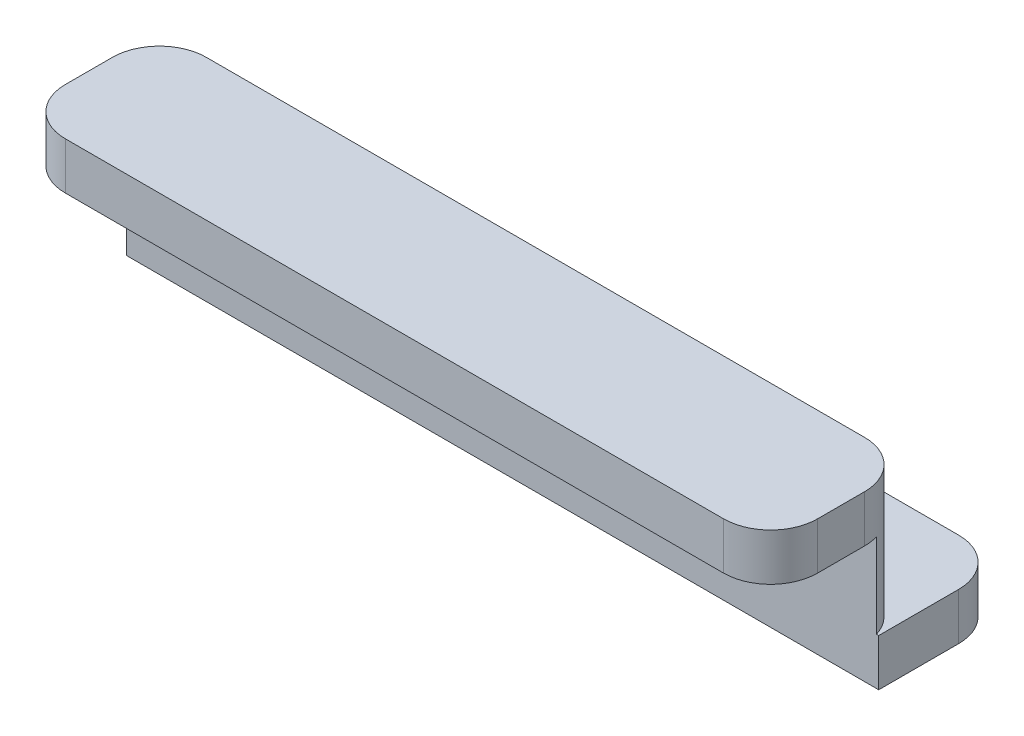
SolidWorks part; units mm, degrees
ref_plane "Front Plane" through (0, 0, 0) normal (0, 0, 1) x (1, 0, 0)
ref_plane "Top Plane" through (0, 0, 0) normal (0, 1, 0) x (1, 0, 0)
ref_plane "Right Plane" through (0, 0, 0) normal (1, 0, 0) x (0, 0, -1)
sketch "Sketch1" plane through (0, 0, 0) normal (0, 1, 0) x (1, 0, 0)
  line L1 (2, 0) -> (30, 0)
  line L2 (0, 2) -> (0, 4)
  line L3 (2, 6) -> (30, 6)
  line L4 (32, 2) -> (32, 4)
  arc A0 (30, 6) -> (32, 4) centre (30, 4) cw
  arc A1 (30, 0) -> (32, 2) centre (30, 2) ccw
  arc A2 (2, 0) -> (0, 2) centre (2, 2) cw
  arc A3 (0, 4) -> (2, 6) centre (2, 4) cw
  point P11 (0, 0)
  dimension "D1" = 2
  dimension "D2" = 2
  dimension "D3" = 32
  dimension "D4" = 6
extrude "Boss-Extrude1" add sketch "Sketch1" along normal blind 2
sketch "Sketch2" plane through (0, 2, 0) normal (0, 1, 0) x (1, 0, 0)
  line L0 (16, 0) -> (16, 10.7795) construction
  line L1 (2, 0) -> (30, 0) construction
  line L2 (32, 4) -> (32, 2)
  line L4 (0, 4) -> (0, 2) construction
  line L5 (30, 6) -> (2, 6) construction
  line L13 (0, 4) -> (0, 2)
  line L14 (30, 6) -> (2, 6)
  line L21 (30.1, 3.1) -> (30.1, 0.0025)
  line L22 (3.4, 4.6) -> (28.6, 4.6)
  line L23 (1.9, 0.0025) -> (1.9, 3.1)
  arc A0 (32, 2) -> (30.1, 0.0025) centre (30, 2) cw
  arc A1 (30, 6) -> (32, 4) centre (30, 4) cw
  arc A3 (2, 6) -> (0, 4) centre (2, 4) ccw construction
  arc A4 (0, 2) -> (2, 0) centre (2, 2) ccw construction
  arc A11 (2, 6) -> (0, 4) centre (2, 4) ccw
  arc A12 (0, 2) -> (1.9, 0.0025) centre (2, 2) ccw
  arc A15 (30.1, 3.1) -> (28.6, 4.6) centre (28.6, 3.1) ccw
  arc A16 (3.4, 4.6) -> (1.9, 3.1) centre (3.4, 3.1) ccw
  point P14 (16, 4.9)
  point P18 (32, 3)
  point P32 (16, 6)
  dimension "D2" = 1.9
  dimension "D3" = 1.5
  dimension "D1" = 1.4
extrude "Boss-Extrude2" add sketch "Sketch2" against normal blind 7.6
sketch "Sketch4" plane through (0, -5.6, 0) normal (0, -1, 0) x (1, 0, 0)
  line L5 (30, -6) -> (2, -6) construction
  line L8 (30, -6) -> (2, -6)
  line L9 (0, -4) -> (0, -8)
  line L10 (2, -10) -> (30, -10)
  line L11 (32, -8) -> (32, -4)
  arc A9 (30, -6) -> (32, -4) centre (30, -4) ccw construction
  arc A10 (0, -4) -> (2, -6) centre (2, -4) ccw construction
  arc A11 (30, -6) -> (32, -4) centre (30, -4) ccw
  arc A12 (0, -4) -> (2, -6) centre (2, -4) ccw
  arc A13 (0, -8) -> (2, -10) centre (2, -8) ccw
  arc A14 (30, -10) -> (32, -8) centre (30, -8) ccw
  dimension "D1" = 2
  dimension "D2" = 4
extrude "Boss-Extrude3" add sketch "Sketch4" against normal blind 2
sketch "Sketch5" plane through (0, 0, 0) normal (0, -1, 0) x (1, 0, 0)
  line L0 (0, -8) -> (0, -2) construction
  line L1 (0, 0) -> (32, 0)
  line L2 (0, 0) -> (0, -4.6)
  line L3 (0, -4.6) -> (32, -4.6)
  line L4 (32, 0) -> (32, -4.6)
  line L5 (2, 0) -> (30, 0) construction
  line L6 (3.4, -4.6) -> (28.6, -4.6) construction
  line L7 (32, -2) -> (32, -8) construction
extrude "Cut-Extrude1" cut sketch "Sketch5" along normal through all
